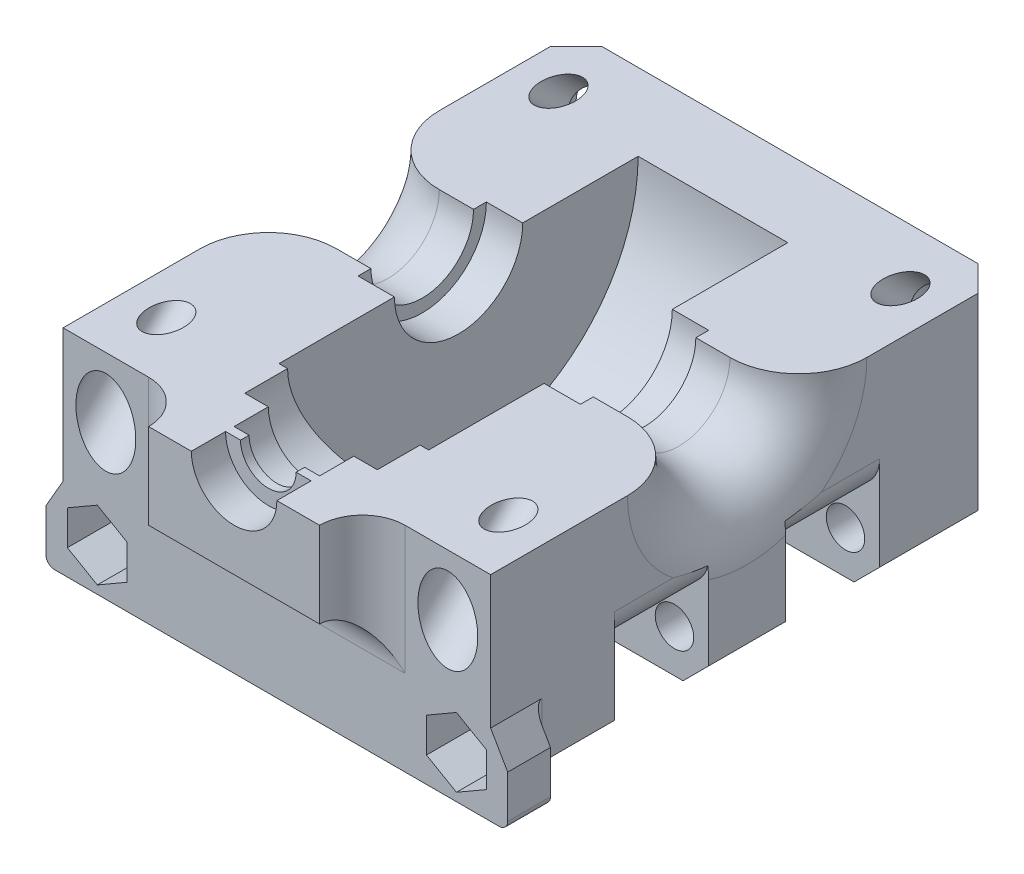
SolidWorks part; units mm, degrees
other "Markup1"
sketch "Sketch20" plane through (27, 25.293, 30) normal (0.4941, 0.7903, 0.3623) x (0.77, -0.2044, -0.6044)
ref_plane "Front Plane" through (0, 0, 0) normal (0, 0, 1) x (1, 0, 0)
ref_plane "Top Plane" through (0, 0, 0) normal (0, 1, 0) x (1, 0, 0)
ref_plane "Right Plane" through (0, 0, 0) normal (1, 0, 0) x (0, 0, -1)
sketch "Sketch1" plane through (0, 0, 0) normal (0, 1, 0) x (1, 0, 0)
  line L1 (-25, 30) -> (25, 30)
  line L2 (-25, 30) -> (-25, -30)
  line L3 (-25, -30) -> (25, -30)
  line L4 (25, 30) -> (25, -30)
  line L5 (-25, 30) -> (25, -30) construction
  line L6 (-25, -30) -> (25, 30) construction
  point P0 (0, 0)
  dimension "D1" = 50
  dimension "D2" = 60
extrude "Boss-Extrude1" add sketch "Sketch1" along normal blind 25
sketch "Sketch2" plane through (-25, 0, 0) normal (-1, 0, 0) x (0, 0, 1)
  line L3 (-30, 25) -> (30, 25) construction
  line L6 (-30, 25) -> (-30, 0) construction
  circle A1 centre (0, 25) radius 21
  dimension "D1" = 42
  dimension "D2" = 9
extrude "Cut-Extrude1" cut sketch "Sketch2" against normal blind 17.5 from offset 16.25 offset against normal yes
sketch "Sketch3" plane through (-25, 0, 0) normal (-1, 0, 0) x (0, 0, 1)
  line L0 (-30, 25) -> (30, 25) construction
  circle A0 centre (0, 25) radius 7.5
  dimension "D1" = 15
extrude "Cut-Extrude2" cut sketch "Sketch3" against normal blind 26 from offset 12 offset against normal yes
sketch "Sketch4" plane through (0, 0, 30) normal (0, 0, 1) x (1, 0, 0)
  line L0 (-25, 25) -> (25, 25) construction
  circle A0 centre (0, 25) radius 5
  dimension "D1" = 10
extrude "Cut-Extrude3" cut sketch "Sketch4" against normal blind 4
sketch "Sketch10" plane through (25, 0, 0) normal (1, 0, 0) x (0, 0, -1)
  line L0 (-30, 0) -> (30, 0) construction
  line L1 (-4.5, 0) -> (-15.5, 0)
  line L2 (-4.5, 0) -> (-4.5, 10)
  line L3 (-4.5, 10) -> (-15.5, 10)
  line L4 (-15.5, 0) -> (-15.5, 10)
  line L5 (-30, 25) -> (-30, 0) construction
  line L6 (4.5, 0) -> (15.5, 0)
  line L7 (4.5, 0) -> (4.5, 10)
  line L8 (4.5, 10) -> (15.5, 10)
  line L9 (15.5, 0) -> (15.5, 10)
  arc A1 (7.5, 25) -> (-7.5, 25) centre (0, 25) ccw construction
  dimension "D1" = 10
  dimension "D2" = 10
  dimension "D3" = 9
  dimension "D4" = 11
  dimension "D5" = 11
  dimension "D6" = 14.5
  dimension "D7" = 4.5
  dimension "D8" = 4.5
extrude "Cut-Extrude9" cut sketch "Sketch10" against normal blind 11
sketch "Sketch11" plane through (0, 0, -4.5) normal (0, 0, -1) x (-1, 0, 0)
  line L0 (-25, 10) -> (-25, 0) construction
  line L1 (-14, 0) -> (-25, 0) construction
  circle A0 centre (-21, 5) radius 2.25
  dimension "D3" = 4.5
  dimension "D1" = 4
  dimension "D2" = 5
extrude "Cut-Extrude10" cut sketch "Sketch11" against normal through all both and the other way through all
mirror "Mirror1" about plane through (0, 0, 0) normal (1, 0, 0) of "Cut-Extrude9", "Cut-Extrude10"
ref_plane "Plane1" through (0, -2.5, 2.5) normal (0, -0.7071, 0.7071) x (1, 0, 0)
sketch "Sketch12" plane through (0, -2.5, 2.5) normal (0, -0.7071, 0.7071) x (1, 0, 0)
  line L0 (-25, 38.8909) -> (-25, 21.2132) construction
  line L2 (-25, 38.8909) -> (-5, 38.8909) construction
  line L3 (5, 38.8909) -> (25, 38.8909) construction
  circle A0 centre (20, 33.8909) radius 2
  circle A1 centre (-20, 33.8909) radius 2
  dimension "D1" = 4
  dimension "D2" = 4
  dimension "D3" = 40
  dimension "D4" = 5
  dimension "D5" = 5
  dimension "D6" = 5
extrude "Cut-Extrude11" cut sketch "Sketch12" against normal through all both and the other way through all
sketch "Sketch13" plane through (0, -2.5, 2.5) normal (0, -0.7071, 0.7071) x (1, 0, 0)
  circle A0 centre (-20, 33.8909) radius 3.5
  circle A1 centre (20, 33.8909) radius 3.5
  dimension "D1" = 7
  dimension "D2" = 7
extrude "Cut-Extrude12" cut sketch "Sketch13" along normal through all
mirror "Mirror3" about plane through (0, 0, 0) normal (0, 0, 1) of "Cut-Extrude12", "Cut-Extrude11"
chamfer "Chamfer1" distance 3 angle 45 2 edges at (25, 12.5, -30) (-25, 12.5, -30)
fillet "Fillet1" radius 4 4 edges at (25, 10, 10) (25, 10, -10) (-25, 10, -10) (-25, 10, 10)
sketch "Sketch14" plane through (0, 0, 0) normal (0, -1, 0) x (1, 0, 0)
  circle A0 centre (-15, -20.2057) radius 1.8
  circle A1 centre (15, -20.2057) radius 1.8
  dimension "D1" = 3.6
  dimension "D2" = 3.6
  dimension "D3" = 30
  dimension "D4" = 15
extrude "Cut-Extrude13" cut sketch "Sketch14" against normal blind 10
sketch "Sketch15" plane through (0, 0, 30) normal (0, 0, 1) x (1, 0, 0)
  line L1 (-21, 0.9585) -> (-17.5, 2.9793)
  line L2 (-17.5, 2.9793) -> (-17.5, 7.0207)
  line L3 (-17.5, 7.0207) -> (-21, 9.0415)
  line L4 (-21, 9.0415) -> (-24.5, 7.0207)
  line L5 (-24.5, 7.0207) -> (-24.5, 2.9793)
  line L6 (-24.5, 2.9793) -> (-21, 0.9585)
  line L7 (21, 0.9585) -> (24.5, 2.9793)
  line L8 (24.5, 2.9793) -> (24.5, 7.0207)
  line L9 (24.5, 7.0207) -> (21, 9.0415)
  line L10 (21, 9.0415) -> (17.5, 7.0207)
  line L11 (17.5, 7.0207) -> (17.5, 2.9793)
  line L12 (17.5, 2.9793) -> (21, 0.9585)
  circle A0 centre (-21, 5) radius 3.5 construction
  circle A1 centre (21, 5) radius 3.5 construction
  dimension "D1" = 7
  dimension "D2" = 7
extrude "Cut-Extrude14" cut sketch "Sketch15" against normal blind 7
sketch "Sketch16" plane through (0, 0, 30) normal (0, 0, 1) x (1, 0, 0)
  line L0 (-25, 9.4641) -> (-27, 6)
  line L1 (-25, 25) -> (-25, 0) construction
  line L2 (-27, 6) -> (-27, 1)
  line L5 (-15.5359, 0) -> (-25, 0)
  line L6 (-25, 0) -> (25, 0) construction
  line L7 (-25, 0) -> (-25, 9.4641)
  line L8 (-26, 0) -> (-25, 0)
  arc A1 (-27, 1) -> (-26, 0) centre (-26, 1) ccw
  line M21 (-25, 25) -> (-25, 0)
  dimension "D1" = 1
  dimension "D4" = 2
  dimension "D6" = 4
extrude "Boss-Extrude2" add sketch "Sketch16" against normal blind 5 contours L2 A1 L8 L0 M21 region at (-25.9134, 3.9829, 30)
mirror "Mirror4" about plane through (0, 0, 0) normal (1, 0, 0) of "Boss-Extrude2"
chamfer "Chamfer2" distance 3 angle 45 9 edges at (-25, 0, 20.25) (-25, 0, 0) (-25, 0, -21.25) (-23.5, 0, -28.5) (0, 0, -30) (23.5, 0, -28.5) (25, 0, -21.25) (25, 0, 20.25) (25, 0, 0)
fillet "Fillet2" radius 1 4 edges at (23.5, 1.5, 25) (25, 6.2321, 25) (-25, 6.2321, 25) (-23.5, 1.5, 25)
sketch "Sketch17" plane through (-25, 0, 0) normal (-1, 0, 0) x (0, 0, 1)
  circle A0 centre (0, 25) radius 6
  dimension "D1" = 12
extrude "Cut-Extrude15" cut sketch "Sketch17" against normal through all both and the other way through all
fillet "Fillet3" radius 8 2 edges at (25, 19, 0) (-25, 19, 0)
sketch "Sketch21" plane through (0, 0, 26) normal (0, 0, 1) x (1, 0, 0)
  line L0 (-5, 25) -> (5, 25) construction
  circle A0 centre (0, 25) radius 7.75
  dimension "D1" = 15.5
extrude "Cut-Extrude16" cut sketch "Sketch21" against normal blind 8
sketch "Sketch22" plane through (0, 0, 30) normal (0, 0, 1) x (1, 0, 0)
  line L0 (-25, 25) -> (-5, 25) construction
  line L1 (-10, 25) -> (10, 25)
  line L2 (-10, 25) -> (-10, 15)
  line L3 (-10, 15) -> (10, 15)
  line L4 (10, 25) -> (10, 15)
  dimension "D1" = 10
  dimension "D2" = 5
  dimension "D3" = 5
extrude "Boss-Extrude3" add sketch "Sketch22" along normal blind 5
sketch "Sketch23" plane through (0, 0, 35) normal (0, 0, 1) x (1, 0, 0)
  line L0 (10, 25) -> (-10, 25) construction
  circle A0 centre (0, 25) radius 3.25
  dimension "D1" = 6.5
extrude "Cut-Extrude17" cut sketch "Sketch23" against normal blind 5
sketch "Sketch24" plane through (0, 0, 35) normal (0, 0, 1) x (1, 0, 0)
  line L0 (8.75, 25) -> (-8.75, 25) construction
  circle A0 centre (0, 25) radius 5
  dimension "D1" = 10
extrude "Cut-Extrude18" cut sketch "Sketch24" against normal blind 4
fillet "Fillet4" radius 5 3 edges at (-10, 20, 30) (0, 15, 30) (10, 20, 30)
sketch "Sketch25" plane through (0, 0, 0) normal (0, -1, 0) x (1, 0, 0)
  line L0 (-10, 35) -> (10, 35) construction
  circle A0 centre (10, 23) radius 1.5
  circle A1 centre (-10, 23) radius 1.5
  circle A2 centre (10, 13) radius 1.5
  circle A3 centre (-10, 13) radius 1.5
  dimension "D5" = 3
  dimension "D6" = 3
  dimension "D7" = 3
  dimension "D8" = 3
  dimension "D1" = 10
  dimension "D2" = 10
  dimension "D3" = 20
  dimension "D4" = 20
  dimension "D9" = 10
  dimension "D10" = 12
extrude "Cut-Extrude19" cut sketch "Sketch25" against normal blind 8
sketch "Sketch26" plane through (0, 0, -30) normal (0, 0, -1) x (-1, 0, 0)
  circle A0 centre (21, 5) radius 3.6
  circle A1 centre (-21, 5) radius 3.6
  dimension "D1" = 7.2
  dimension "D2" = 7.2
extrude "Cut-Extrude20" cut sketch "Sketch26" against normal blind 10
equation "\"D2@Sketch25\"=\"D1@Sketch25\""
equation "\"D4@Sketch25\"=\"D3@Sketch25\""
